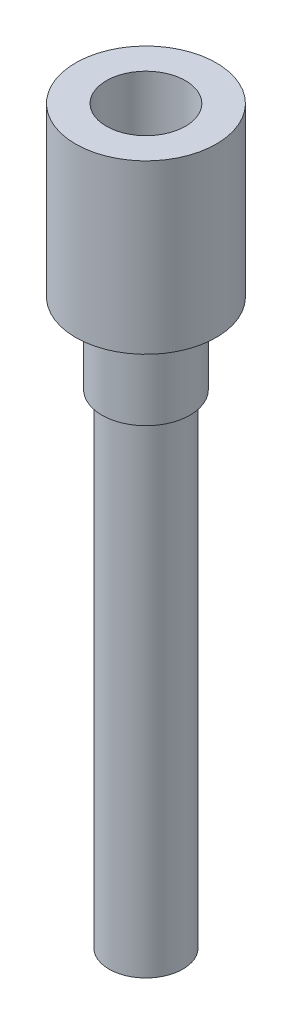
SolidWorks part; units mm, degrees
material "1023 Carbon Steel Sheet (SS)"
ref_plane "Front Plane" through (0, 0, 0) normal (0, 0, 1) x (1, 0, 0)
ref_plane "Top Plane" through (0, 0, 0) normal (0, 1, 0) x (1, 0, 0)
ref_plane "Right Plane" through (0, 0, 0) normal (1, 0, 0) x (0, 0, -1)
sketch "Sketch1" plane through (0, 0, 0) normal (0, 1, 0) x (1, 0, 0)
  circle A0 centre (0, 0) radius 2.58
  circle A1 centre (0, 0) radius 5.5
  circle A2 centre (0, 0) radius 4.58 construction
  dimension "D1" = 2
  dimension "D2" = 11
  dimension "D3" = 5.16
  dimension "D4" = 9.16
extrude "Boss-Extrude1" add sketch "Sketch1" along normal blind 72.14
sketch "Sketch2" plane through (0, 0, 0) normal (0, -1, 0) x (1, 0, 0)
  circle A0 centre (0, 0) radius 5.5
  circle A1 centre (0, 0) radius 5.5 construction
  circle A2 centre (0, 0) radius 5.5
  dimension "D1" = 11
sketch "Sketch4" plane through (0, 72.14, 0) normal (0, 1, 0) x (1, 0, 0)
  circle A0 centre (0, 0) radius 3.4
  circle A2 centre (0, 0) radius 5.5 construction
  dimension "D1" = 6.8
  dimension "D2" = 2.1
sketch "Sketch5" plane through (0, 72.14, 0) normal (0, 1, 0) x (1, 0, 0)
  circle A0 centre (0, 0) radius 6.5785
  circle M3 centre (0, 0) radius 5.5
  circle M4 centre (0, 0) radius 2.58
  dimension "D1" = 13.157
extrude "Boss-Extrude2" add sketch "Sketch5" along normal blind 12 contours M3 | A0 M3 | M4 region at (-6.3924, 72.14, 0) region at (-5.3444, 72.14, 0) region at (0, 72.14, 0)
sketch "Sketch6" plane through (0, 84.14, 0) normal (0, 1, 0) x (1, 0, 0)
  circle A0 centre (0, 0) radius 10.5
  circle M9 centre (0, 0) radius 6.5785
  dimension "D1" = 21
extrude "Boss-Extrude3" add sketch "Sketch6" along normal blind 25 contours A0 | M9 region at (-10.203, 84.14, 0) region at (0, 84.14, 0)
hole_wizard "G1/4 Tapped Hole2" positions "Sketch10" profile "Sketch11" tap size "G1/4" standard "ISO"
sketch "Sketch10" plane through (0, 109.14, 0) normal (0, 1, 0) x (1, 0, 0)
  point P0 (0, 0)
sketch "Sketch11" plane through (0, 109.14, 0) normal (1, 0, 0) x (0, 0, 1)
  line L0 (0, 0) -> (0, 23.5451)
  line L1 (0, 23.5451) -> (5.9, 20)
  line L2 (5.9, 20) -> (5.9, 0)
  line L5 (5.9, 0) -> (0, 0)
  line L10 (0, 23.5451) -> (-5.9, 20) construction
  line L11 (0, -6.35) -> (0, 107.95) construction
  dimension "Tap Drill Dia." = 11.8
  dimension "Tap Drill Depth" = 20
  dimension "Drill Angle" = 118
cosmetic thread "Hole Thread7" parameters "D1"=15, "D2"=13.157
ref_plane "Plane1" through (0, 90.14, 0) normal (0, -1, 0) x (-1, 0, 0)
sketch "Sketch15" plane through (0, 90.14, 0) normal (0, -1, 0) x (-1, 0, 0)
  circle A0 centre (0, 0) radius 2.5
  dimension "D1" = 5
extrude "Boss-Extrude4" add sketch "Sketch15" along normal up to surface (18 mm away) contours A0 region at (0, 90.14, 0) up to face at (0, 72.14, 2.58)
hole_wizard "M8 Tapped Hole1" positions "Sketch16" profile "Sketch17" tap size "M8" standard "ISO"
sketch "Sketch16" plane through (0, 90.14, 0) normal (0, 1, 0) x (1, 0, 0)
  point P0 (0, 0)
sketch "Sketch17" plane through (0, 90.14, 0) normal (1, 0, 0) x (0, 0, 1)
  line L0 (0, 0) -> (0, 81.1829)
  line L1 (0, 81.1829) -> (3.4, 79.14)
  line L2 (3.4, 79.14) -> (3.4, 0)
  line L5 (3.4, 0) -> (0, 0)
  line L10 (0, 81.1829) -> (-3.4, 79.14) construction
  line L11 (0, -6.35) -> (0, 107.95) construction
  dimension "Tap Drill Dia." = 6.8
  dimension "Tap Drill Depth" = 79.14
  dimension "Drill Angle" = 118
cosmetic thread "Hole Thread2" parameters "D1"=10, "D2"=8
sketch "Sketch18" plane through (0, 0, 0) normal (0, 0, 1) x (1, 0, 0)
  line L0 (0, 87.14) -> (0, 91.64) construction
  line L2 (5.9, 87.14) -> (-5.9, 87.14) construction
  circle A0 centre (0, 91.64) radius 4.5
  point P7 (0, 87.14)
  dimension "D2" = 9
equation "\"D1@Sketch6\"=21"
